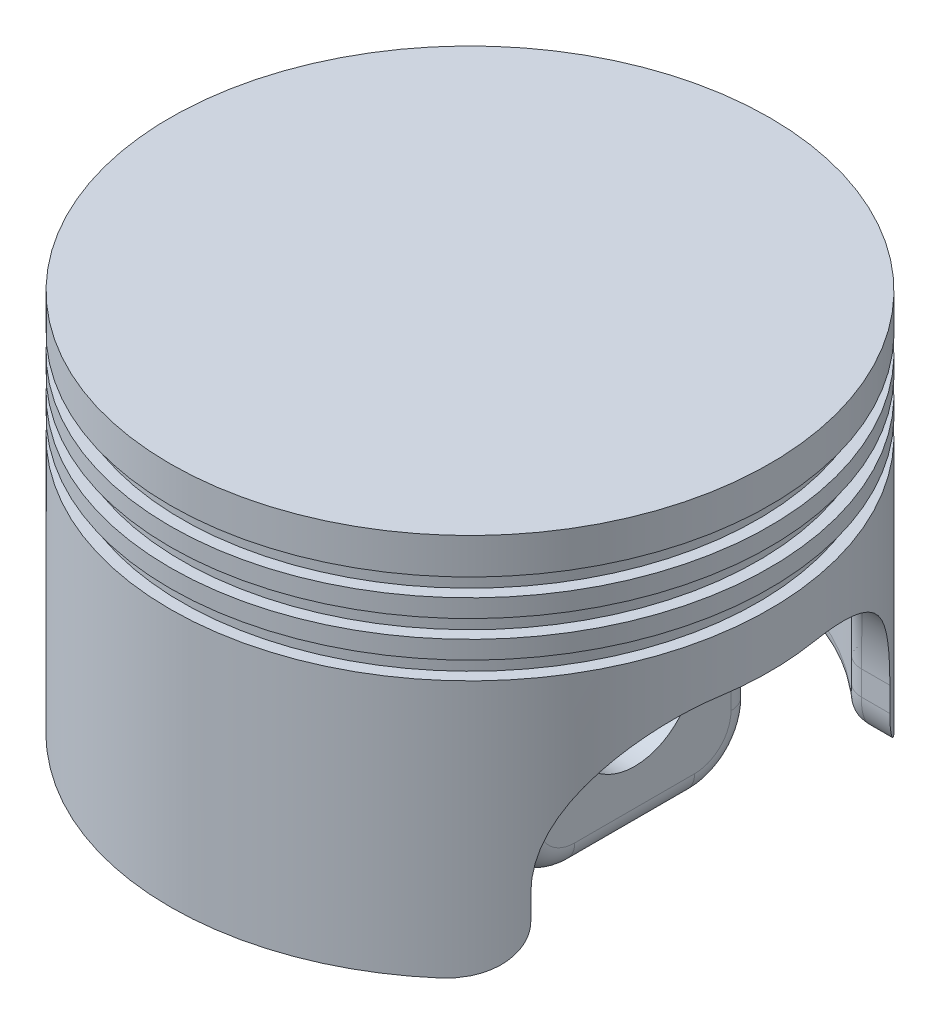
SolidWorks part; units mm, degrees
ref_plane "Front Plane" through (0, 0, 0) normal (0, 0, 1) x (1, 0, 0)
ref_plane "Top Plane" through (0, 0, 0) normal (0, 1, 0) x (1, 0, 0)
ref_plane "Right Plane" through (0, 0, 0) normal (1, 0, 0) x (0, 0, -1)
sketch "Sketch1" plane through (0, 0, 0) normal (1, 0, 0) x (0, 0, -1)
  line L0 (0, 0) -> (63.5, 0)
  line L1 (63.5, 0) -> (63.5, -81.28)
  line L2 (63.5, -81.28) -> (57.15, -81.28)
  line L3 (57.15, -81.28) -> (57.15, -19)
  line L4 (57.15, -19) -> (0, -19)
  line L5 (0, -19) -> (0, 0)
  dimension "D1" = 63.5
  dimension "D2" = 81.28
  dimension "D3" = 19
  dimension "D4" = 6.35
revolve "Revolve1" add sketch "Sketch1" angle 360 about L5
sketch "Sketch2" plane through (0, 0, 0) normal (0, 0, 1) x (1, 0, 0)
  line L0 (63.54, -7.62) -> (61, -7.62)
  line L1 (61, -7.62) -> (61, -11.43)
  line L2 (61, -11.43) -> (63.54, -11.43)
  line L3 (63.5, 0) -> (-63.5, 0) construction
  line L4 (63.54, -11.43) -> (63.54, -7.62)
  dimension "D1" = 3.81
  dimension "D2" = 7.62
  dimension "D3" = 2.54
  dimension "D4" = 63.54
ref_axis "Axis1" through (0, -85.344, 0) along (0, 1, 0)
revolve "Cut-Revolve1" cut sketch "Sketch2" angle 360 about axis through (0, -85.344, 0) along (0, 1, 0)
pattern_linear "LPattern1" count 3 spacing 7.62 along (0, -1, 0) of "Cut-Revolve1"
sketch "Sketch4" plane through (0, 0, 0) normal (1, 0, 0) x (0, 0, -1)
  line L0 (63.5, 0) -> (-63.5, 0) construction
  line L1 (-57.15, -81.28) -> (57.15, -81.28) construction
  line L2 (-38, -38.1) -> (38.2, -38.1)
  line L3 (-38, -38.1) -> (-38, -81.28)
  line L4 (-38, -81.28) -> (38.2, -81.28)
  line L5 (38.2, -38.1) -> (38.2, -81.28)
  line L6 (0, -85.344) -> (0, 4.064) construction
  dimension "D1" = 38.1
  dimension "D2" = 76.2
  dimension "D3" = 38
extrude "Cut-Extrude1" cut sketch "Sketch4" against normal through all both and the other way through all
fillet "Fillet1" radius 28 4 edges at (-46.7806, -38.1, 38) (-46.6161, -38.1, -38.2) (46.6161, -38.1, -38.2) (46.7806, -38.1, 38)
sketch "Sketch5" plane through (0, -19, 0) normal (0, -1, 0) x (1, 0, 0)
  line L1 (-15.88, -25.4) -> (-34.88, -25.4)
  line L2 (-15.88, -25.4) -> (-15.88, 25.4)
  line L3 (-15.88, 25.4) -> (-34.88, 25.4)
  line L4 (-34.88, -25.4) -> (-34.88, 25.4)
  line L5 (-15.88, -25.4) -> (-34.88, 25.4) construction
  line L6 (-15.88, 25.4) -> (-34.88, -25.4) construction
  point P0 (-25.38, 0)
  point P5 (0, 0)
  dimension "D1" = 19
  dimension "D2" = 15.88
  dimension "D3" = 50.8
extrude "Boss-Extrude1" add sketch "Sketch5" along normal blind 63.5
mirror "Mirror1" about plane through (0, 0, 0) normal (1, 0, 0) of "Boss-Extrude1"
sketch "Sketch6" plane through (-34.88, 0, 0) normal (-1, 0, 0) x (0, 0, 1)
  line L0 (0, -85.344) -> (0, 4.064) construction
  line L1 (25.4, -82.5) -> (-25.4, -82.5) construction
  circle A0 centre (0, -57.1) radius 12.7
  point P7 (0, 0)
  dimension "D2" = 25.4
  dimension "D1" = 25.4
extrude "Cut-Extrude2" cut sketch "Sketch6" against normal through all both and the other way through all
fillet "Fillet2" radius 12.7 4 edges at (25.38, -82.5, 25.4) (-25.38, -82.5, 25.4) (-25.38, -82.5, -25.4) (25.38, -82.5, -25.4)
fillet "Fillet3" radius 10 4 edges at (-46.7806, -81.28, 38) (-46.6161, -81.28, -38.2) (46.6161, -81.28, -38.2) (46.7806, -81.28, 38)
fillet "Fillet4" radius 5 20 edges at (-34.88, -44.4, 25.4) (-34.88, -78.7803, 21.6803) (-34.88, -44.4, -25.4) (-34.88, -78.7803, -21.6803) (-15.88, -44.4, -25.4) (-15.88, -78.7803, -21.6803) (-15.88, -44.4, 25.4) (-15.88, -78.7803, 21.6803) (15.88, -44.4, -25.4) (15.88, -78.7803, -21.6803) (15.88, -44.4, 25.4) (15.88, -78.7803, 21.6803) (34.88, -44.4, 25.4) (34.88, -78.7803, 21.6803) (34.88, -44.4, -25.4) (34.88, -78.7803, -21.6803) (-34.88, -82.5, 0) (-15.88, -82.5, 0) (15.88, -82.5, 0) (34.88, -82.5, 0)
fillet "Fillet5" radius 5 16 edges at (-17.3445, -19, -23.9355) (-25.38, -19, -25.4) (-33.4155, -19, -23.9355) (-34.88, -19, 0) (-33.4155, -19, 23.9355) (-25.38, -19, 25.4) (-17.3445, -19, 23.9355) (33.4155, -19, 23.9355) (25.38, -19, 25.4) (17.3445, -19, 23.9355) (15.88, -19, 0) (17.3445, -19, -23.9355) (25.38, -19, -25.4) (33.4155, -19, -23.9355) (-15.88, -19, 0) (34.88, -19, 0)
fillet "Fillet6" radius 5 1 edges at (0, -19, -57.15)
fillet "Fillet8" radius 5 16 edges at (50.4876, -43.6844, 26.7792) (42.6863, -68.69, 38) (41.4568, -76.2764, 39.3377) (0, -81.28, 57.15) (-40.0962, -78.1397, 40.7237) (-42.6863, -68.69, 38) (-46.1361, -51.2346, 33.728) (-57.1499, -38.1, -0.1016) (-50.3758, -43.6917, -26.9889) (-42.5074, -68.69, -38.2) (-41.2742, -76.2619, -39.5293) (0, -81.28, -57.15) (39.9078, -78.1233, -40.9083) (42.5074, -68.69, -38.2) (45.9735, -51.2686, -33.9493) (57.1499, -38.1, -0.1016)
